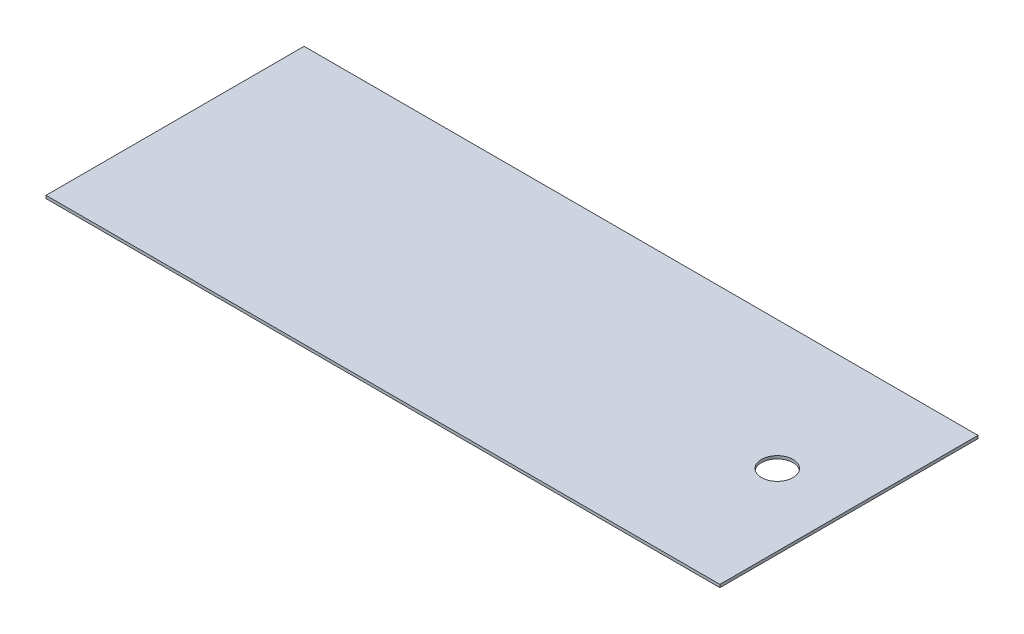
SolidWorks part; units mm, degrees
material "Pino"
ref_plane "Alzado" through (0, 0, 0) normal (0, 0, 1) x (1, 0, 0)
ref_plane "Planta" through (0, 0, 0) normal (0, 1, 0) x (1, 0, 0)
ref_plane "Vista lateral" through (0, 0, 0) normal (1, 0, 0) x (0, 0, -1)
sketch "Sketch1" plane through (0, 0, 0) normal (0, 1, 0) x (1, 0, 0)
  line L1 (-235, -90) -> (235, -90)
  line L2 (-235, -90) -> (-235, 90)
  line L3 (-235, 90) -> (235, 90)
  line L4 (235, -90) -> (235, 90)
  line L5 (-235, -90) -> (235, 90) construction
  line L6 (-235, 90) -> (235, -90) construction
  point P0 (0, 0)
  dimension "D1" = 470
  dimension "D2" = 180
base flange "Base-Flange1" sketch "Sketch1" thickness 2 reverse thickness direction no parameters "D1"=1
sketch "Sketch10" plane through (0, 0, 0) normal (0, 1, 0) x (1, 0, 0)
  line L0 (235, -90) -> (235, 90) construction
  circle A0 centre (185, 0) radius 11
  dimension "D1" = 22
  dimension "D2" = 50
extrude "Extrude1" cut sketch "Sketch10" against normal blind 10 contours A0
sketch "Sketch3" [suppressed] plane through (0, 0, 0) normal (0, 1, 0) x (1, 0, 0)
sketch "Sketch5" [suppressed] plane through (0, 0, 0) normal (0, 1, 0) x (1, 0, 0)
sheet metal parameters "Sheet-Metal2" thickness 2 parameters "D1"=1
flat pattern "Flat-Pattern2" [suppressed]
sketch "Sketch7" plane through (0, 0, 0) normal (0, 1, 0) x (1, 0, 0)
sketch3d "Sketch9" [suppressed]
  line L0 (-230, 90, 0) -> (230, 90, 0) construction
  line L1 (-230, -90, 0) -> (230, -90, 0) construction
  line L2 (-230, 90, 0) -> (-230, -90, 0) construction
  line L3 (230, 90, 0) -> (230, -90, 0) construction
sheet metal parameters "Sheet-Metal3" thickness 2 parameters "D1"=1
flat pattern "Flat-Pattern2"
sketch "Sketch7" plane through (0, 0, 0) normal (0, 1, 0) x (1, 0, 0)
sketch3d "Sketch9" [suppressed]
  line L0 (235, 90, 0) -> (-235, 90, 0) construction
  line L1 (235, -90, 0) -> (-235, -90, 0) construction
  line L2 (235, 90, 0) -> (235, -90, 0) construction
  line L3 (-235, 90, 0) -> (-235, -90, 0) construction
